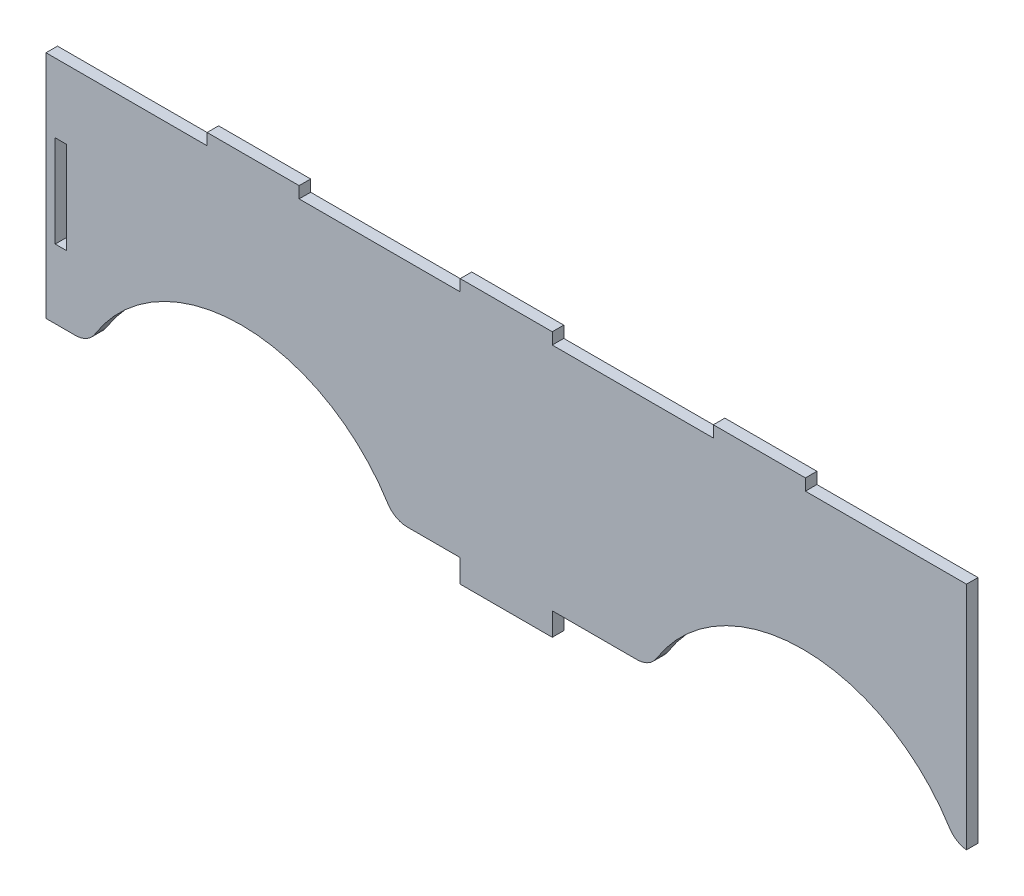
SolidWorks part; units mm, degrees
material "Maple"
ref_plane "Front Plane" through (0, 0, 0) normal (0, 0, 1) x (1, 0, 0)
ref_plane "Top Plane" through (0, 0, 0) normal (0, 1, 0) x (1, 0, 0)
ref_plane "Right Plane" through (0, 0, 0) normal (1, 0, 0) x (0, 0, -1)
sketch "Sketch1" plane through (0, 0, 0) normal (0, 0, 1) x (1, 0, 0)
  line L1 (-100, -25) -> (-100, 25) construction
  line L2 (0, -25) -> (0, 25) construction
  line L3 (-100, 25) -> (0, 25) construction
  line L4 (-100, -25) -> (0, 25) construction
  line L5 (0, -25) -> (-100, 25) construction
  line L6 (-102.5, 27.5) -> (0, 27.5) construction
  line L7 (24.4075, -25) -> (-24.4075, -25) construction
  line L8 (-102.5, -30) -> (6.0068, -30) construction
  line L9 (-102.5, -27.5) -> (-102.5, 27.5) construction
  line L10 (-98, -10) -> (-95.5, -10)
  line L11 (-98, -10) -> (-98, 10)
  line L12 (-98, 10) -> (-95.5, 10)
  line L13 (-95.5, -10) -> (-95.5, 10)
  line L14 (-98, -10) -> (-95.5, 10) construction
  line L15 (-98, 10) -> (-95.5, -10) construction
  line L16 (-90.74, -25) -> (-100, -25) construction
  line L17 (-100, -25) -> (-100, 25)
  line L18 (-100, 25) -> (-65, 25)
  line L19 (-65, 25) -> (-65, 27.5)
  line L20 (-65, 27.5) -> (-45, 27.5)
  line L21 (-45, 27.5) -> (-45, 25)
  line L22 (-45, 25) -> (-10, 25)
  line L23 (-10, 25) -> (-10, 27.5)
  line L24 (-10, 27.5) -> (10, 27.5)
  line L29 (-10, -25) -> (-10, -30)
  line L30 (-10, -30) -> (10, -30)
  line L35 (10, 25) -> (10, 27.5)
  line L36 (45, 25) -> (10, 25)
  line L37 (45, 27.5) -> (45, 25)
  line L38 (65, 27.5) -> (45, 27.5)
  line L39 (65, 25) -> (65, 27.5)
  line L40 (100, 25) -> (65, 25)
  line L41 (100, -25) -> (100, 25)
  line L44 (10, -30) -> (10, -25)
  line L56 (-10, -25) -> (-24.4075, -25)
  line L57 (-100, -25) -> (0, -25) construction
  line L58 (-90.74, -25) -> (-100, -25)
  line L60 (31.2875, -25) -> (10, -25)
  line L61 (-102.5, -27.5) -> (0, -27.5) construction
  line L62 (-19.6475, -25) -> (-19.6475, -10) construction
  line L63 (26.5275, -25) -> (26.5275, -7.347) construction
  line L64 (97.62, -25) -> (100, -25)
  arc A0 (-90.74, -25) -> (-24.4075, -25) centre (-57.5738, -42.5) cw
  arc A2 (31.2875, -25) -> (97.62, -25) centre (64.4538, -42.5) cw
  point P0 (-96.75, 0)
  point P1 (-50, 0)
  point P42 (0, -30)
  dimension "D6" = 37.5
  dimension "D11" = 2.38
  dimension "D16" = 37.5
  dimension "D1" = 50
  dimension "D2" = 2.5
  dimension "D3" = 20
  dimension "D4" = 2.5
  dimension "D5" = 2
  dimension "D7" = 9.26
  dimension "D8" = 200
  dimension "D9" = 5
  dimension "D10" = 20
  dimension "D12" = 12.5
  dimension "D13" = 4.76
  dimension "D14" = 12.5
  dimension "D15" = 4.76
extrude "Boss-Extrude1" add sketch "Sketch1" along normal mid plane 2.5
fillet "Fillet2" radius 5 4 edges at (97.62, -25, 0) (31.2875, -25, 0) (-24.4075, -25, 0) (-90.74, -25, 0)
sketch "Sketch2" plane through (0, 0, -1.25) normal (0, 0, -1) x (-1, 0, 0)
  line L0 (-100, -25) -> (-100, 25) construction
  line L1 (-21.19, -11.1) -> (-9.19, -11.1)
  line L2 (-21.19, -11.1) -> (-21.19, -22)
  line L3 (-21.19, -22) -> (-9.19, -22)
  line L4 (-9.19, -11.1) -> (-9.19, -22)
  line L5 (-21.19, -11.1) -> (-9.19, -22) construction
  line L6 (-21.19, -22) -> (-9.19, -11.1) construction
  line L7 (-10, -25) -> (-28.3982, -25) construction
  line L9 (10.01, -22) -> (18.91, -22)
  line L10 (10.01, -22) -> (10.01, -11.1)
  line L11 (10.01, -11.1) -> (18.91, -11.1)
  line L12 (18.91, -22) -> (18.91, -11.1)
  line L13 (10.01, -22) -> (18.91, -11.1) construction
  line L14 (10.01, -11.1) -> (18.91, -22) construction
  point P0 (-15.19, -16.55)
  point P9 (14.46, -16.55)
  dimension "D1" = 19.2
  dimension "D2" = 3
  dimension "D3" = 10.9
  dimension "D4" = 12
  dimension "D5" = 110.01
  dimension "D6" = 8.9
extrude "Cut-Extrude1" [suppressed] cut sketch "Sketch2" against normal blind 10 contours L9 L12 L11 L10 | L4 L1 L2 L3
